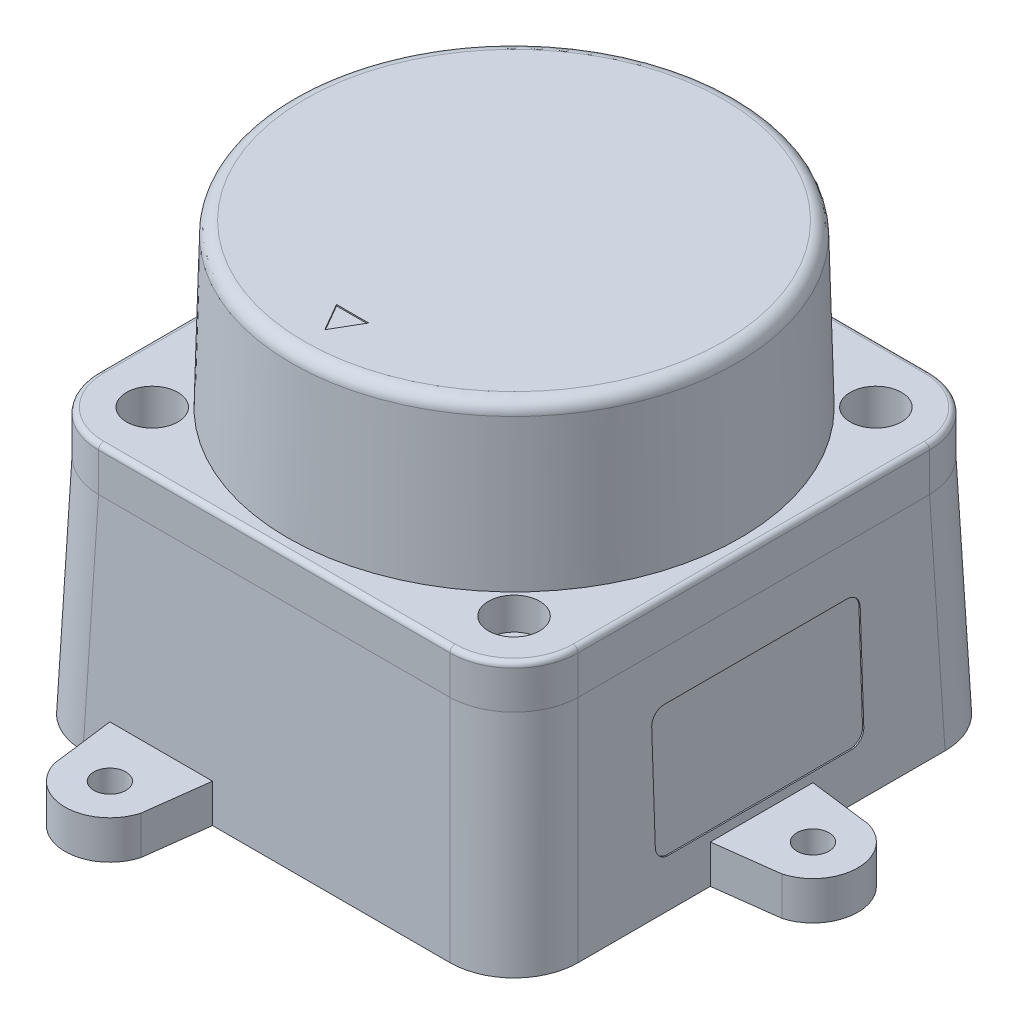
SolidWorks part; units mm, degrees
ref_plane "Front Plane" through (0, 0, 0) normal (0, 0, 1) x (1, 0, 0)
ref_plane "Top Plane" through (0, 0, 0) normal (0, 1, 0) x (1, 0, 0)
ref_plane "Right Plane" through (0, 0, 0) normal (1, 0, 0) x (0, 0, -1)
sketch "Sketch1" plane through (0, 0, 0) normal (0, 1, 0) x (1, 0, 0)
  line L0 (-19.295, 0) -> (19.295, 0) construction
  line L1 (-19.295, 19.295) -> (19.295, 19.295)
  line L2 (-19.295, 19.295) -> (-19.295, -19.295)
  line L3 (-19.295, -19.295) -> (19.295, -19.295)
  line L4 (19.295, 19.295) -> (19.295, -19.295)
  line L5 (0, 19.295) -> (0, -19.295) construction
  point P8 (0, 0)
  dimension "D1" = 38.59
  dimension "D2" = 38.59
extrude "Boss-Extrude1" add sketch "Sketch1" along normal blind 17.3 draft 2
sketch "Sketch2" plane through (0, 17.3, 0) normal (0, 1, 0) x (1, 0, 0)
  line L0 (0, 18.6909) -> (0, -18.6909) construction
  line L1 (-18.6909, 18.6909) -> (18.6909, 18.6909)
  line L2 (-18.6909, 18.6909) -> (-18.6909, -18.6909)
  line L3 (-18.6909, -18.6909) -> (18.6909, -18.6909)
  line L4 (18.6909, 18.6909) -> (18.6909, -18.6909)
  line L5 (-18.6909, 0) -> (18.6909, 0) construction
  line L6 (18.6909, -18.6909) -> (18.6909, 18.6909) construction
  line L7 (18.6909, 18.6909) -> (-18.6909, 18.6909) construction
  point P8 (0, 0)
extrude "Boss-Extrude2" add sketch "Sketch2" along normal blind 3.4
sketch "Sketch3" plane through (0, 20.7, 0) normal (0, 1, 0) x (1, 0, 0)
  circle A0 centre (0, 0) radius 17.645
  dimension "D1" = 35.29
extrude "Boss-Extrude3" add sketch "Sketch3" along normal blind 12.6 draft 1.5 contours A0
fillet "Fillet1" radius 5 8 edges at (-18.9929, 8.65, -18.9929) (-18.6909, 19, -18.6909) (18.6909, 19, -18.6909) (18.9929, 8.65, -18.9929) (-18.9929, 8.65, 18.9929) (-18.6909, 19, 18.6909) (18.9929, 8.65, 18.9929) (18.6909, 19, 18.6909)
fillet "Fillet2" radius 0.4 8 edges at (17.2264, 20.7, -17.2264) (0, 20.7, -18.6909) (18.6909, 20.7, 0) (17.2264, 20.7, 17.2264) (0, 20.7, 18.6909) (-17.2264, 20.7, 17.2264) (-18.6909, 20.7, 0) (-17.2264, 20.7, -17.2264)
fillet "Fillet3" radius 1 1 edges at (0, 33.3, 17.3151)
sketch "Sketch4" plane through (0, 33.3, 0) normal (0, 1, 0) x (1, 0, 0)
  line L1 (0, -14.75) -> (1.25, -12.5849)
  line L2 (1.25, -12.5849) -> (-1.25, -12.5849)
  line L3 (-1.25, -12.5849) -> (0, -14.75)
  circle A0 centre (0, -13.3066) radius 1.4434 construction
  dimension "D1" = 14.75
  dimension "D2" = 2.5
extrude "Cut-Extrude1" cut sketch "Sketch4" against normal blind 0.1
sketch "Sketch5" plane through (0, 0, 0) normal (0, 0, 1) x (1, 0, 0)
  line L0 (16.3409, 33.3) -> (-16.3409, 33.3) construction
  circle A0 centre (0, 25.7) radius 4
  dimension "D1" = 7.6
  dimension "D2" = 8
extrude "Cut-Extrude2" [suppressed] cut sketch "Sketch5" against normal blind 0.01 from surface starting at face at (0, 32.3262, -17.3406)
sketch "Sketch6" plane through (0, 0, 0) normal (1, 0, 0) x (0, 0, -1)
  line L0 (-4.625, 3.725) -> (4.625, 3.725) construction
  line L1 (-4.625, 5.85) -> (4.625, 5.85)
  line L2 (-4.625, 5.85) -> (-4.625, 1.6)
  line L3 (-4.625, 1.6) -> (4.625, 1.6)
  line L4 (4.625, 5.85) -> (4.625, 1.6)
  line L5 (0, 5.85) -> (0, 1.6) construction
  line L6 (-14.298, 0) -> (14.298, 0) construction
  point P8 (0, 3.725)
  dimension "D1" = 9.25
  dimension "D2" = 4.25
  dimension "D3" = 1.6
extrude "Cut-Extrude3" cut sketch "Sketch6" along normal blind 7 from offset 19.295 offset against normal yes
sketch "Sketch15" plane through (0, 0, 0) normal (1, 0, 0) x (0, 0, -1)
  line L0 (-8.125, 8.6) -> (8.125, 8.6) construction
  line L1 (-8.125, 13.6) -> (8.125, 13.6)
  line L2 (-8.125, 13.6) -> (-8.125, 3.6)
  line L3 (-8.125, 3.6) -> (8.125, 3.6)
  line L4 (8.125, 13.6) -> (8.125, 3.6)
  line L5 (0, 13.6) -> (0, 3.6) construction
  line L6 (-14.298, 0) -> (14.298, 0) construction
  point P8 (0, 8.6)
  dimension "D1" = 3.6
  dimension "D2" = 10
  dimension "D3" = 16.25
extrude "Cut-Extrude4" cut sketch "Sketch15" against normal blind 0.1 from surface starting at face at (18.8922, 11.5333, 0)
fillet "Fillet4" radius 1 4 edges at (19.1193, 3.6, -8.125) (18.7701, 13.6, -8.125) (18.7701, 13.6, 8.125) (19.1193, 3.6, 8.125)
sketch "Sketch10" plane through (0, 20.7, 0) normal (0, 1, 0) x (1, 0, 0)
  line L0 (0, 18.2909) -> (0, -18.2909) construction
  line L1 (13.6909, 18.2909) -> (-13.6909, 18.2909) construction
  line L2 (-13.6909, -18.2909) -> (13.6909, -18.2909) construction
  line L3 (18.2909, 0) -> (-18.2909, 0) construction
  line L4 (18.2909, -13.6909) -> (18.2909, 13.6909) construction
  line L5 (-18.2909, 13.6909) -> (-18.2909, -13.6909) construction
  circle A0 centre (-14.1, 14.1) radius 2
  circle A1 centre (14.1, -14.1) radius 2
  dimension "D1" = 14.1
  dimension "D5" = 4
  dimension "D2" = 14.1
  dimension "D3" = 14.1
  dimension "D4" = 14.1
extrude "Cut-Extrude5" cut sketch "Sketch10" against normal blind 2.5
sketch "Sketch12" plane through (0, 18.2, 0) normal (0, 1, 0) x (1, 0, 0)
  circle A0 centre (14.1, -14.1) radius 1
  circle A1 centre (-14.1, 14.1) radius 1
  circle A2 centre (-14.1, 14.1) radius 2 construction
  circle A3 centre (14.1, -14.1) radius 2 construction
  dimension "D1" = 2
extrude "Cut-Extrude6" cut sketch "Sketch12" against normal blind 6
sketch "Sketch7" plane through (0, 20.7, 0) normal (0, 1, 0) x (1, 0, 0)
  line L0 (0, 18.2909) -> (0, -18.2909) construction
  line L1 (13.6909, 18.2909) -> (-13.6909, 18.2909) construction
  line L2 (-13.6909, -18.2909) -> (13.6909, -18.2909) construction
  line L3 (18.2909, 0) -> (-18.2909, 0) construction
  line L4 (18.2909, -13.6909) -> (18.2909, 13.6909) construction
  line L5 (-18.2909, 13.6909) -> (-18.2909, -13.6909) construction
  circle A0 centre (-14.1, -14.1) radius 2
  circle A1 centre (14.1, 14.1) radius 2
  dimension "D1" = 4
  dimension "D3" = 14.1
  dimension "D4" = 14.1
  dimension "D5" = 14.1
  dimension "D6" = 14.1
extrude "Cut-Extrude7" cut sketch "Sketch7" against normal blind 7.9
sketch "Sketch13" plane through (0, 12.8, 0) normal (0, 1, 0) x (1, 0, 0)
  circle A0 centre (-14.1, -14.1) radius 1.25
  circle A1 centre (-14.1, -14.1) radius 2 construction
  circle A2 centre (14.1, 14.1) radius 1.25
  circle A3 centre (14.1, 14.1) radius 2 construction
  dimension "D1" = 2.5
extrude "Cut-Extrude8" cut sketch "Sketch13" against normal blind 1
sketch "Sketch14" plane through (0, 11.8, 0) normal (0, 1, 0) x (1, 0, 0)
  circle A0 centre (-14.1, -14.1) radius 2.4
  circle A1 centre (-14.1, -14.1) radius 1.25 construction
  circle A2 centre (14.1, 14.1) radius 2.4
  circle A3 centre (14.1, 14.1) radius 1.25 construction
  dimension "D1" = 4.8
extrude "Cut-Extrude9" cut sketch "Sketch14" against normal blind 11.8
sketch "Sketch16" plane through (0, 0, 0) normal (0, -1, 0) x (1, 0, 0)
  line L0 (0, 19.295) -> (0, -19.295) construction
  line L1 (-14.298, 19.295) -> (14.298, 19.295) construction
  line L2 (14.298, -19.295) -> (-14.298, -19.295) construction
  line L3 (19.295, 0) -> (-19.295, 0) construction
  line L4 (19.295, 14.298) -> (19.295, -14.298) construction
  line L5 (-19.295, -14.298) -> (-19.295, 14.298) construction
  circle A0 centre (-15.7, -15.7) radius 1.25
  dimension "D1" = 2.5
  dimension "D2" = 15.7
  dimension "D3" = 15.7
extrude "Cut-Extrude10" cut sketch "Sketch16" against normal blind 5.8
sketch "Sketch18" plane through (0, 0, 0) normal (0, -1, 0) x (1, 0, 0)
  line L0 (0, 0) -> (37.5773, 0) construction
  line L1 (19.295, 14.298) -> (19.295, -14.298) construction
  line L2 (19.295, 4) -> (24.2546, 3.3659)
  line L3 (19.295, -4) -> (24.2546, -3.3659)
  line L4 (19.295, 4) -> (19.295, -4)
  line L5 (-8.205, -27.6396) -> (-8.205, 26.5495) construction
  line L6 (-14.298, 19.295) -> (14.298, 19.295) construction
  line L7 (-4.8391, 24.2546) -> (-4.205, 19.295)
  line L8 (-4.205, 19.295) -> (-12.205, 19.295)
  line L9 (-12.205, 19.295) -> (-11.5709, 24.2546)
  line L10 (-12.205, -19.295) -> (-11.5709, -24.2546)
  line L11 (-4.205, -19.295) -> (-12.205, -19.295)
  line L12 (-4.8391, -24.2546) -> (-4.205, -19.295)
  circle A0 centre (23.295, 0) radius 1.25
  arc A1 (24.2546, -3.3659) -> (24.2546, 3.3659) centre (23.295, 0) ccw
  circle A2 centre (-8.205, 23.295) radius 1.25
  arc A3 (-4.8391, 24.2546) -> (-11.5709, 24.2546) centre (-8.205, 23.295) ccw
  circle A4 centre (-8.205, -23.295) radius 1.25
  arc A5 (-4.8391, -24.2546) -> (-11.5709, -24.2546) centre (-8.205, -23.295) cw
  dimension "D1" = 2.5
  dimension "D3" = 7
  dimension "D7" = 2.5
  dimension "D8" = 7
  dimension "D2" = 4
  dimension "D4" = 8
  dimension "D5" = 27.5
  dimension "D6" = 4
  dimension "D9" = 5
  dimension "D10" = 8
  dimension "D11" = 5
extrude "Boss-Extrude4" add sketch "Sketch18" against normal blind 3 separate body
